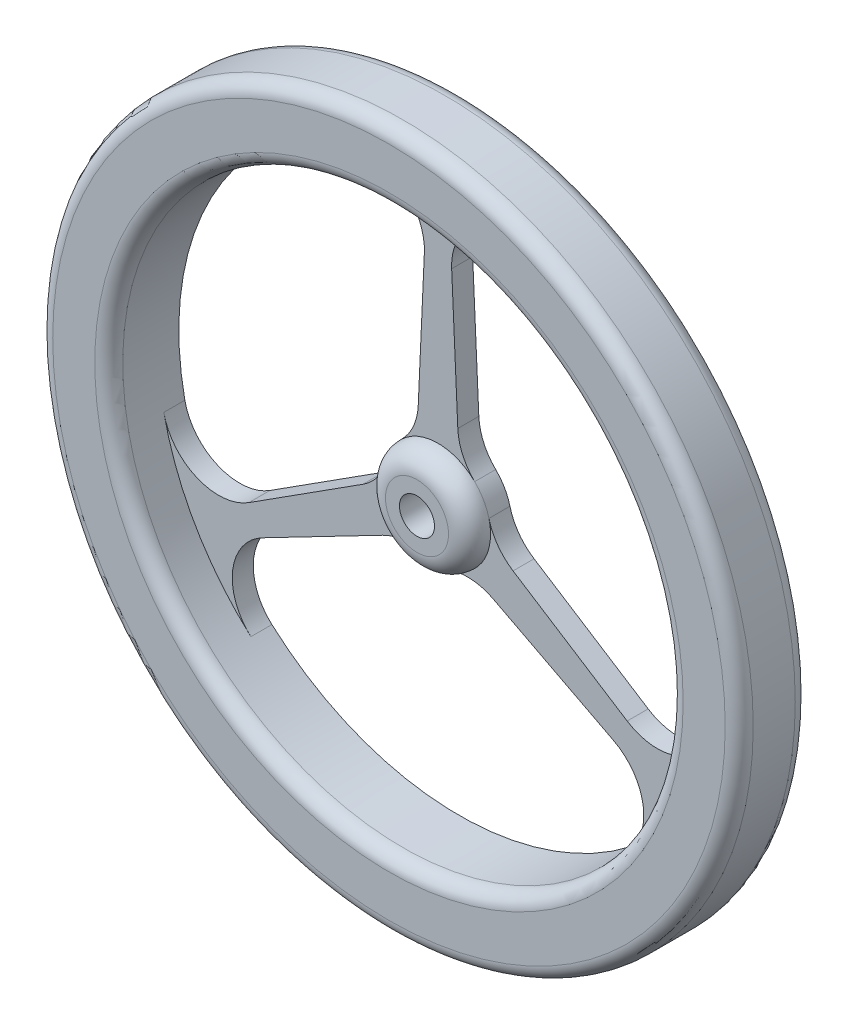
SolidWorks part; units mm, degrees
ref_plane "Front Plane" through (0, 0, 0) normal (0, 0, 1) x (1, 0, 0)
ref_plane "Top Plane" through (0, 0, 0) normal (0, 1, 0) x (1, 0, 0)
ref_plane "Right Plane" through (0, 0, 0) normal (1, 0, 0) x (0, 0, -1)
sketch "Sketch1" plane through (0, 0, 0) normal (0, 0, 1) x (1, 0, 0)
  circle A0 centre (0, 0) radius 50
  dimension "D1" = 100
extrude "Extrude-Thin1" add sketch "Sketch1" along normal blind 10 thin thin type one direction reverse wall 10
sketch "Sketch2" plane through (0, 0, 0) normal (0, 0, 1) x (1, 0, 0)
  circle A0 centre (0, 0) radius 7.5
  circle A1 centre (0, 0) radius 2.5
  point P4 (0, 0)
  dimension "D1" = 5
  dimension "D2" = 15
extrude "Boss-Extrude1" add sketch "Sketch2" along normal blind 6 separate body
sketch "Sketch3" plane through (0, 0, 0) normal (0, 0, 1) x (1, 0, 0)
  line L0 (0, -40) -> (0, 40) construction
  line L1 (-1.4997, 39.9719) -> (-3, 6.8739)
  line L2 (1.4997, 39.9719) -> (3, 6.8739)
  line L3 (35.3665, -18.6871) -> (7.4529, -0.8389)
  line L4 (33.8668, -21.2847) -> (4.4529, -6.035)
  line L5 (-33.8668, -21.2847) -> (-4.4529, -6.035)
  line L6 (-35.3665, -18.6871) -> (-7.4529, -0.8389)
  circle A0 centre (0, 0) radius 40
  circle A1 centre (0, 0) radius 40 construction
  circle A2 centre (0, 0) radius 7.5
  circle A3 centre (0, 0) radius 7.5 construction
  point P8 (0, 0)
  point P9 (0, 0)
  point P10 (0, 0)
  point P15 (30.993, 25.2871)
  point P16 (0, 0)
  point P19 (0, 0)
  point P40 (0, 0)
  point P41 (-1.4997, 40)
  dimension "D1" = 1.5
  dimension "D2" = 3
  dimension "D3" = 3
extrude "Boss-Extrude4" add sketch "Sketch3" along normal blind 3 contours A2 L0 A0 L1 | L0 A2 L2 A0 | A2 L4 A0 L3 | A2 L6 A0 L5 region at (-18.9141, -10.9201, 0) region at (18.9141, -10.9201, 0) region at (-1.167, 21.8401, 0) region at (1.167, 21.8401, 0)
fillet "Fillet4" radius 8 12 edges at (35.3665, -18.6871, 1.5) (33.8668, -21.2847, 1.5) (-33.8668, -21.2847, 1.5) (-35.3665, -18.6871, 1.5) (4.4529, -6.035, 1.5) (-4.4529, -6.035, 1.5) (-7.4529, -0.8389, 1.5) (-3, 6.8739, 1.5) (7.4529, -0.8389, 1.5) (3, 6.8739, 1.5) (1.4997, 39.9719, 1.5) (-1.4997, 39.9719, 1.5)
fillet "Fillet2" radius 3 1 edges at (7.5, 0, 6)
fillet "Fillet3" radius 2 3 edges at (50, 0, 0) (50, 0, 10) (40, 0, 10)
